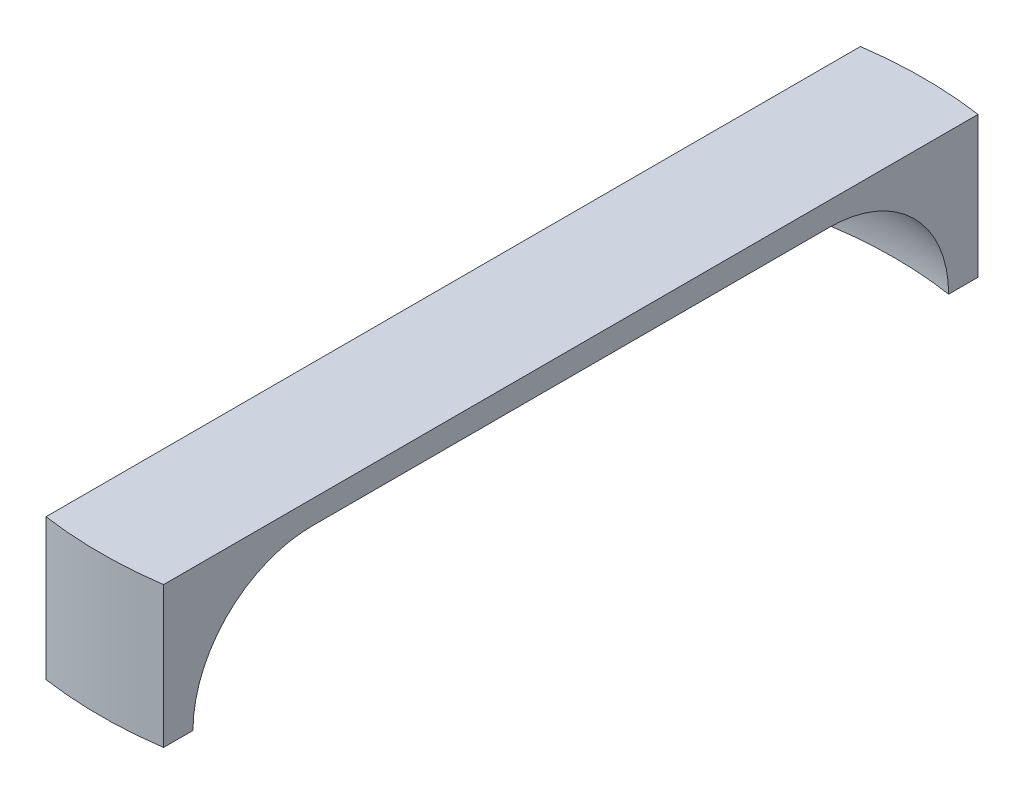
SolidWorks part; units mm, degrees
ref_plane "Ebene vorne" through (0, 0, 0) normal (0, 0, 1) x (1, 0, 0)
ref_plane "Ebene oben" through (0, 0, 0) normal (0, 1, 0) x (1, 0, 0)
ref_plane "Ebene rechts" through (0, 0, 0) normal (1, 0, 0) x (0, 0, -1)
sketch "Skizze1" plane through (0, 0, 0) normal (0, 1, 0) x (1, 0, 0)
  line L2 (-10, 69.282) -> (-10, -69.282)
  line L4 (10, 69.282) -> (10, -69.282)
  line L5 (-10, 69.282) -> (10, -69.282) construction
  line L6 (-10, -69.282) -> (10, 69.282) construction
  circle A0 centre (0, 0) radius 70 construction
  arc A1 (10, 69.282) -> (-10, 69.282) centre (0, 0) ccw
  arc A2 (10, -69.282) -> (-10, -69.282) centre (0, 0) cw
  point P4 (0, 0)
  point P9 (0, 0)
  point P10 (-10.0001, 69.282)
  point P11 (-10.8577, 82.6404)
  point P12 (0, 0)
  point P13 (10.0002, 69.282)
  point P14 (11.3364, 52.7496)
  point P15 (-9.962, -68.2218)
  dimension "D1" = 140
  dimension "D2" = 20
extrude "Aufsatz-Linear austragen1" add sketch "Skizze1" along normal blind 4
sketch "Skizze2" plane through (0, 0, 0) normal (0, -1, 0) x (1, 0, 0)
  line L0 (-10, -69.282) -> (-10, 69.282) construction
  line L1 (10, 69.282) -> (10, -69.282) construction
  line L2 (-10, 69.282) -> (-10, 64.282)
  line L3 (10, 69.282) -> (10, 64.282)
  line L4 (-10, -64.282) -> (-10, -69.282)
  line L5 (10, -64.282) -> (10, -69.282)
  arc A0 (-10, -69.282) -> (10, -69.282) centre (0, 0) ccw construction
  arc A1 (10, 69.282) -> (-10, 69.282) centre (0, 0) ccw construction
  arc A2 (-10, -69.282) -> (10, -69.282) centre (0, 0) ccw
  arc A3 (10, 69.282) -> (-10, 69.282) centre (0, 0) ccw
  arc A4 (-10, 64.282) -> (10, 64.282) centre (0, 0) cw
  arc A5 (10, -64.282) -> (-10, -64.282) centre (0, 0) cw
  dimension "D1" = 5
extrude "Aufsatz-Linear austragen2" add sketch "Skizze2" along normal blind 20
fillet "Verrundung1" radius 20 2 edges at (0, 0, 65.0552) (0, 0, -65.0552)
